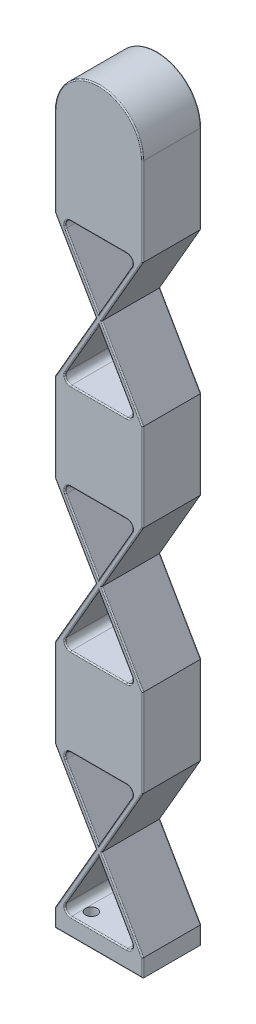
SolidWorks part; units mm, degrees
material "PET"
ref_plane "Front Plane" through (0, 0, 0) normal (0, 0, 1) x (1, 0, 0)
ref_plane "Top Plane" through (0, 0, 0) normal (0, 1, 0) x (1, 0, 0)
ref_plane "Right Plane" through (0, 0, 0) normal (1, 0, 0) x (0, 0, -1)
sketch "Sketch1" plane through (0, 0, 0) normal (0, 0, 1) x (1, 0, 0)
  line L0 (0, 0) -> (57.9688, 0) construction
  line L1 (7.5, 12.1244) -> (-7.5, 12.1244)
  line L2 (7.5, -27.1244) -> (-7.5, -27.1244)
  line L3 (7.5, -27.1244) -> (7.5, -12.1244)
  line L4 (7.5, -12.1244) -> (-7.5, -12.1244)
  line L5 (-7.5, -27.1244) -> (-7.5, -12.1244)
  line L6 (7.5, -27.1244) -> (-7.5, -12.1244) construction
  line L7 (7.5, -12.1244) -> (-7.5, -27.1244) construction
  line L8 (-7.5, 27.1244) -> (-7.5, 12.1244)
  line L9 (0, 0) -> (0, 41.5625) construction
  line L10 (7.5, 27.1244) -> (-7.5, 27.1244)
  line L11 (7.5, 27.1244) -> (7.5, 12.1244)
  line L12 (-7.5, 12.1244) -> (6.5, -12.1244)
  line L13 (6.5, -12.1244) -> (7.5, -12.1244)
  line L14 (7.5, -12.1244) -> (-6.5, 12.1244)
  line L15 (-6.5, 12.1244) -> (-7.5, 12.1244)
  line L16 (7.5, 12.1244) -> (-6.5, -12.1244)
  line L17 (-7.5, -12.1244) -> (6.5, 12.1244)
  point P1 (0, -19.6244)
  dimension "D1" = 15
  dimension "D2" = 60
  dimension "D3" = 1
extrude "Boss-Extrude1" add sketch "Sketch1" along normal mid plane 10 contours L5 L2 L3 L4 region at (0, -19.6244, 0)
extrude "Boss-Extrude2" add sketch "Sketch1<3>" against normal up to surface (5 mm away) from surface contours L17 L4 L16 L12 | L17 L14 L16 L1 | L17 L12 L16 L14 region at (3.6296, 6.276, 0) region at (0, 0, 0) region at (-3.6296, -6.276, 0) up to face at (0, -19.6244, -5) starting at face at (0, -19.6244, 5)
sketch "Sketch1<3>" plane through (0, 0, 0) normal (0, 0, 1) x (1, 0, 0) same geometry as "Sketch1"
extrude "Boss-Extrude3" add sketch "Sketch1<4>" along normal up to surface (5 mm away) from surface contours L12 L17 L14 L1 | L14 L16 L12 L4 | L17 L12 L16 L14 region at (0, 0, 0) region at (3.6296, -6.276, 0) region at (-3.6296, 6.276, 0) up to face at (1.0714, -9.4819, 5) starting at face at (1.0714, -9.4819, -5)
sketch "Sketch1<4>" plane through (0, 0, 0) normal (0, 0, 1) x (1, 0, 0) same geometry as "Sketch1"
extrude "Boss-Extrude4" add sketch "Sketch1<5>" along normal mid plane 10 contours L11 L10 L8 L1 region at (0, 19.6244, 0)
sketch "Sketch1<5>" plane through (0, 0, 0) normal (0, 0, 1) x (1, 0, 0) same geometry as "Sketch1"
ref_plane "Plane1" through (0, 19.6244, 0) normal (0, -1, 0) x (-1, 0, 0)
ref_plane "Plane2" through (7.5, -27.1244, 5) normal (-1, 0, 0) x (0, 0, 1)
ref_plane "Plane3" through (0, -19.6244, 0) normal (0, 1, 0) x (1, 0, 0)
mirror "Mirror2" about plane through (0, 19.6244, 0) normal (0, -1, 0) of "Boss-Extrude2", "Boss-Extrude3"
mirror "Mirror3" about plane through (0, 19.6244, 0) normal (0, -1, 0) of "Boss-Extrude1"
mirror "Mirror4" about plane through (0, -19.6244, 0) normal (0, 1, 0) of "Boss-Extrude2"
mirror "Mirror5" about plane through (0, -19.6244, 0) normal (0, 1, 0) of "Boss-Extrude3"
mirror "Mirror6" about plane through (0, -19.6244, 0) normal (0, 1, 0) of "Boss-Extrude4"
sketch "Sketch2" plane through (0, 0, 0) normal (0, 0, 1) x (1, 0, 0)
  line L0 (-7.5, 51.3731) -> (-7.5, 66.3731)
  line L1 (-7.5, 51.3731) -> (-7.5, 66.3731)
  line L2 (-7.5, 66.3731) -> (7.5, 66.3731)
  line L3 (-7.5, 66.3731) -> (7.5, 66.3731)
  line L4 (7.5, 66.3731) -> (7.5, 51.3731)
  line L5 (7.5, 66.3731) -> (7.5, 51.3731)
  line L6 (7.5, 51.3731) -> (0.5, 39.2487)
  line L7 (7.5, 51.3731) -> (0.5, 39.2487)
  line L8 (-7.5, -51.3731) -> (-0.5, -39.2487)
  line L10 (7.5, 27.1244) -> (7.5, 12.1244)
  line L11 (7.5, 27.1244) -> (7.5, 12.1244)
  line L12 (-0.5, -39.2487) -> (-7.5, -27.1244)
  line L14 (0.5, 0) -> (7.5, -12.1244)
  line L15 (0.5, 0) -> (7.5, -12.1244)
  line L16 (7.5, -12.1244) -> (7.5, -27.1244)
  line L17 (7.5, -12.1244) -> (7.5, -27.1244)
  line L18 (7.5, -27.1244) -> (0.5, -39.2487)
  line L20 (-7.5, -27.1244) -> (-7.5, -12.1244)
  line L21 (-7.5, -27.1244) -> (-7.5, -12.1244)
  line L22 (-7.5, -12.1244) -> (-0.5, 0)
  line L24 (-0.5, 0) -> (-7.5, 12.1244)
  line L25 (-0.5, 0) -> (-7.5, 12.1244)
  line L26 (-7.5, 12.1244) -> (-7.5, 27.1244)
  line L27 (-7.5, 12.1244) -> (-7.5, 27.1244)
  line L28 (-7.5, 27.1244) -> (-0.5, 39.2487)
  line L29 (-7.5, 27.1244) -> (-0.5, 39.2487)
  line L30 (-0.5, 39.2487) -> (-7.5, 51.3731)
  line L32 (7.5, 58.8731) -> (2, 58.8731)
  line L33 (0, 56.8731) -> (0, 51.3731)
  line L34 (7.5, -51.3731) -> (7.5, -66.3731)
  line L35 (0.5, 39.2487) -> (7.5, 27.1244)
  line L41 (7.5, -27.1244) -> (0.5, -39.2487)
  line L42 (7.5, -66.3731) -> (-7.5, -66.3731)
  line L43 (7.5, 12.1244) -> (0.5, 0)
  line L44 (-7.5, -66.3731) -> (-7.5, -51.3731)
  line L47 (7.5, -51.3731) -> (7.5, -66.3731)
  line L48 (7.5, -66.3731) -> (-7.5, -66.3731)
  line L49 (-7.5, -66.3731) -> (-7.5, -51.3731)
  line L51 (0.5, -39.2487) -> (7.5, -51.3731)
  line L52 (6.5, -12.1244) -> (-6.5, -12.1244) construction
  line L53 (6.5, 12.1244) -> (-6.5, 12.1244) construction
  line L54 (6.5, 51.3731) -> (-6.5, 51.3731) construction
  line L55 (-7.5, -51.3731) -> (-0.5, -39.2487)
  line L56 (-0.5, -39.2487) -> (-7.5, -27.1244)
  line L57 (6.5, 27.1244) -> (-6.5, 27.1244) construction
  line L58 (-7.5, -12.1244) -> (-0.5, 0)
  line L59 (0, 27.1244) -> (0, 12.1244)
  line L60 (0, -12.1244) -> (0, -27.1244)
  line L61 (6.5, -27.1244) -> (-6.5, -27.1244) construction
  line L62 (-0.5, 39.2487) -> (-7.5, 51.3731)
  line L67 (0.5, 39.2487) -> (7.5, 27.1244)
  line L69 (7.5, 12.1244) -> (0.5, 0)
  line L73 (0.5, -39.2487) -> (7.5, -51.3731)
  arc A0 (2, 58.8731) -> (0, 56.8731) centre (2, 56.8731) ccw
  point P18 (0, -12.1244)
  point P25 (0, 12.1244)
  point P33 (0, 51.3731)
  point P36 (0, 27.1244)
  dimension "D1" = 2
sweep "Cut-Sweep1" [suppressed] cut path "Sketch2" circular profile diameter 3.5 parameters "D3"=3.5
sketch "Sketch10" plane through (0, 0, 0) normal (0, 0, 1) x (1, 0, 0)
  line L0 (0, 17.6244) -> (0, 12.1244)
  line L2 (-5.5, 19.6244) -> (5.5, 19.6244) construction
  line L3 (2, 19.6244) -> (7.5, 19.6244)
  line L4 (7.5, 27.1244) -> (7.5, 12.1244) construction
  line L5 (7.5, 27.1244) -> (7.5, 12.1244) construction
  line L6 (6.5, 12.1244) -> (-6.5, 12.1244) construction
  arc A0 (0, 17.6244) -> (2, 19.6244) centre (2, 17.6244) cw
  point P17 (0, 19.6244)
  dimension "D1" = 2
sweep "Cut-Sweep3" [suppressed] cut path "Sketch10" circular profile diameter 3.5 parameters "D3"=3.5
sketch "Sketch29" plane through (0, 0, 5) normal (0, 0, 1) x (1, 0, 0)
  line L0 (7.5, 66.3731) -> (-7.5, 66.3731) construction
  line L1 (7.5, 66.3731) -> (-7.5, 66.3731)
  arc A0 (-7.5, 66.3731) -> (7.5, 66.3731) centre (0, 66.3731) cw
  line M10 (7.5, 66.3731) -> (-7.5, 66.3731)
extrude "Boss-Extrude5" add sketch "Sketch29" against normal up to surface (10 mm away) contours A0 M10 region at (0, 69.5562, 5) up to face at (0, -47.6203, -5)
ref_plane "Plane4" through (0, -54.3731, 0) normal (0, 1, 0) x (1, 0, 0)
sketch "Sketch36" plane through (0, -54.3731, 0) normal (0, 1, 0) x (1, 0, 0)
  line L4 (7.5, -5) -> (7.5, 5)
  line L5 (7.5, 5) -> (-7.5, 5)
  line L6 (-7.5, 5) -> (-7.5, -5)
  line L7 (-7.5, -5) -> (7.5, -5)
  line L8 (7.5, -5) -> (7.5, 5)
  line L9 (7.5, 5) -> (-7.5, 5)
  line L10 (-7.5, 5) -> (-7.5, -5)
  line L11 (-7.5, -5) -> (7.5, -5)
  dimension "D1" = 0
extrude "Cut-Extrude1" cut sketch "Sketch36" against normal through all
sketch "Sketch38" plane through (0, 0, 5) normal (0, 0, 1) x (1, 0, 0)
  line L0 (0, -54.3731) -> (0, -22.6244)
  line L1 (5.5, -54.3731) -> (-5.5, -54.3731) construction
  line L2 (5.5, -19.6244) -> (-5.5, -19.6244) construction
  line L3 (3, -19.6244) -> (7.5, -19.6244)
  line L4 (7.5, 27.8756) -> (7.5, -82.1244) construction
  arc A0 (0, -22.6244) -> (3, -19.6244) centre (3, -22.6244) cw
  point P12 (0, -19.6244)
  dimension "D1" = 3
sketch "Sketch47" plane through (0, 0, 0) normal (0, 0, 1) x (1, 0, 0)
  line L0 (0, -54.3731) -> (0, -22.6244) construction
  line L2 (0, -54.3731) -> (0, -21.6244)
  line L4 (5.5, -19.6244) -> (-5.5, -19.6244) construction
  line L6 (2, -19.6244) -> (7.5, -19.6244)
  line L7 (7.5, -27.1244) -> (7.5, -12.1244) construction
  arc A1 (0, -21.6244) -> (2, -19.6244) centre (2, -21.6244) cw
  point P7 (0, -19.6244)
  dimension "D1" = 2
sweep "Cut-Sweep5" [suppressed] cut path "Sketch47" circular profile diameter 3.5 parameters "D3"=3.5
fillet "Fillet1" radius 1 12 edges at (-6.5, -12.1244, 0) (6.5, -12.1244, 0) (-6.5, 12.1244, 0) (6.5, 12.1244, 0) (6.5, 51.3731, 0) (-6.5, 51.3731, 0) (6.5, 27.1244, 0) (-6.5, 27.1244, 0) (-6.5, -51.3731, 0) (6.5, -51.3731, 0) (6.5, -27.1244, 0) (-6.5, -27.1244, 0)
sketch "Sketch48" plane through (0, -51.3731, 0) normal (0, 1, 0) x (1, 0, 0)
  line L0 (0, 0) -> (-7.5, -5) construction
  line L1 (-7.5, -5) -> (7.5, -5) construction
  line L2 (0, 0) -> (-3.3333, 5) construction
  line L3 (7.5, 5) -> (-7.5, 5) construction
  circle A0 centre (-3.75, -2.5) radius 1
  circle A1 centre (3.75, 2.5) radius 1
  point P6 (-3.75, -2.5)
  point P9 (3.75, 2.5)
  dimension "D1" = 2
hole_wizard "Ø2.0 mm Dowel Holes1" positions "Sketch48" profile "Sketch49" hole size "Ø2.0" standard "DIN" end condition through all
sketch "Sketch49" plane through (3.75, -51.3731, -2.5) normal (1, 0, 0) x (0, 0, 1)
  line L0 (0, 0) -> (0, 3)
  line L1 (0, 3) -> (1, 3)
  line L2 (1, 3) -> (1, 0)
  line L5 (1, 0) -> (0, 0)
  line L11 (0, -6.35) -> (0, 107.95) construction
  dimension "Thru Hole Dia." = 2
  dimension "Thru Hole Depth" = 3
fillet "Fillet2" radius 0.2 104 edges at (0, -51.3731, -5) (-5.634, -50.8731, -5) (-2.817, -44.9939, -5) (4, -33.1865, -5) (7.5, -19.6244, -5) (4, -6.0622, -5) (-2.817, 5.7452, -5) (-5.634, 11.6244, -5) (0, 12.1244, -5) (7.5, 19.6244, -5) (0, 27.1244, -5) (-5.634, 27.6244, -5) (4, 45.3109, -5) (-2.817, 33.5035, -5) (7.5, 58.8731, -5) (0, 73.8731, -5) (-7.5, 58.8731, -5) (0, 51.3731, -5) (5.634, 50.8731, -5) (-4, 33.1865, -5) (2.817, 44.9939, -5) (-7.5, 19.6244, -5) (-4, 6.0622, -5) (2.817, -5.7452, -5) (5.634, -11.6244, -5) (0, -12.1244, -5) (-7.5, -19.6244, -5) (0, -27.1244, -5) (5.634, -27.6244, -5) (-4, -45.3109, -5) (2.817, -33.5035, -5) (-7.5, -52.8731, -5) (0, -54.3731, -5) (7.5, -52.8731, -5) (-7.5, -52.8731, 5) (0, -51.3731, 5) (5.634, -50.8731, 5) (-4, -33.1865, 5) (2.817, -44.9939, 5) (-7.5, -19.6244, 5) (-4, -6.0622, 5) (2.817, 5.7452, 5) (5.634, 11.6244, 5) (0, 12.1244, 5) (-7.5, 19.6244, 5) (0, 27.1244, 5) (5.634, 27.6244, 5) (-4, 45.3109, 5) (2.817, 33.5035, 5) (-7.5, 58.8731, 5) (0, 73.8731, 5) (7.5, 58.8731, 5) (0, 51.3731, 5) (-5.634, 50.8731, 5) (4, 33.1865, 5) (-2.817, 44.9939, 5) (7.5, 19.6244, 5) (4, 6.0622, 5) (-2.817, -5.7452, 5) (-5.634, -11.6244, 5) (0, -12.1244, 5) (7.5, -19.6244, 5) (0, -27.1244, 5) (-5.634, -27.6244, 5) (4, -45.3109, 5) (-2.817, -33.5035, 5) (7.5, -52.8731, 5) (0, -54.3731, 5) (5.634, 11.6244, -5) (2.817, 5.7452, -5) (-5.634, -11.6244, -5) (-2.817, -5.7452, -5) (5.634, 27.6244, -5) (2.817, 33.5035, -5) (-2.817, 44.9939, -5) (-5.634, 50.8731, -5) (-5.634, -27.6244, -5) (-2.817, -33.5035, -5) (4, -45.3109, -5) (4, 6.0622, -5) (4, 33.1865, -5) (-4, 45.3109, -5) (-4, -6.0622, -5) (-4, -33.1865, -5) (2.817, -44.9939, -5) (5.634, -50.8731, -5) (5.634, -11.6244, 5) (2.817, -5.7452, 5) (-5.634, 11.6244, 5) (-2.817, 5.7452, 5) (-5.634, 27.6244, 5) (-2.817, 33.5035, 5) (2.817, 44.9939, 5) (5.634, 50.8731, 5) (5.634, -27.6244, 5) (2.817, -33.5035, 5) (-2.817, -44.9939, 5) (-5.634, -50.8731, 5) (-4, -45.3109, 5) (-4, 6.0622, 5) (-4, 33.1865, 5) (4, 45.3109, 5) (4, -6.0622, 5) (4, -33.1865, 5)
equation "\"a\"= 3.25"
equation "\"D1@Boss-Extrude2\"=\"a\""
equation "\"D1@Boss-Extrude3\"= \"a\""
equation "\"d_sheath\"= 3.5'M2 threaded inserts"
equation "\"r\"= 2'fillet radius for tendon routing"
equation "\"D3@Cut-Sweep5\"=\"d_sheath\""
equation "\"D1@Sketch2\"=\"r\""
equation "\"D1@Sketch10\"=\"r\""
equation "\"D1@Sketch47\"=\"r\""
